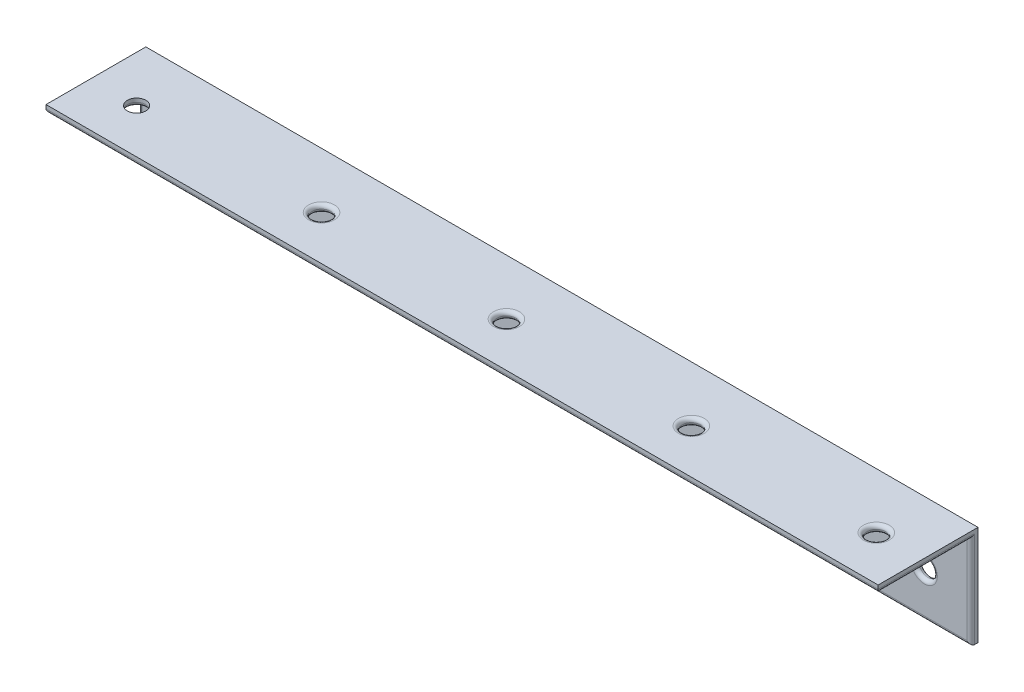
SolidWorks part; units mm, degrees
ref_plane "前视基准面" through (0, 0, 0) normal (0, 0, 1) x (1, 0, 0)
ref_plane "上视基准面" through (0, 0, 0) normal (0, 1, 0) x (1, 0, 0)
ref_plane "右视基准面" through (0, 0, 0) normal (1, 0, 0) x (0, 0, -1)
sketch "草图1" plane through (0, 0, 0) normal (0, 0, 1) x (1, 0, 0)
  line L1 (-112.5, 13.5) -> (112.5, 13.5)
  line L2 (-112.5, 13.5) -> (-112.5, -13.5)
  line L3 (-112.5, -13.5) -> (112.5, -13.5)
  line L4 (112.5, 13.5) -> (112.5, -13.5)
  line L5 (0, -13.5) -> (0, 13.5) construction
  line L6 (-112.5, 0) -> (112.5, 0) construction
  circle A0 centre (-100, -1.5) radius 2.5
  circle A4 centre (-50, -1.5) radius 2.5
  circle A5 centre (0, -1.5) radius 2.5
  circle A6 centre (50, -1.5) radius 2.5
  circle A7 centre (100, -1.5) radius 2.5
  point P0 (0, 0)
  dimension "D3" = 5
  dimension "D1" = 27
  dimension "D2" = 225
  dimension "D4" = 12.5
  dimension "D5" = 12
  dimension "D6" = 5
extrude "凸台-拉伸1" add sketch "草图1" along normal mid plane 2
sketch "草图2" plane through (0, 0, 1) normal (0, 0, 1) x (1, 0, 0)
  line L0 (112.5, -13.5) -> (112.5, 13.5) construction
  line L1 (-112.5, 13.5) -> (112.5, 13.5)
  line L2 (-112.5, 13.5) -> (-112.5, 11.5)
  line L3 (-112.5, 11.5) -> (112.5, 11.5)
  line L4 (112.5, 13.5) -> (112.5, 11.5)
  dimension "D1" = 2
extrude "凸台-拉伸2" add sketch "草图2" along normal blind 25
sketch "草图3" plane through (0, 11.5, 0) normal (0, -1, 0) x (1, 0, 0)
  line L0 (-112.5, 26) -> (112.5, 26) construction
  line L1 (-112.5, 26) -> (-112.5, 1) construction
  circle A0 centre (-100, 14) radius 2.5
  circle A1 centre (-50, 14) radius 2.5
  circle A2 centre (0, 14) radius 2.5
  circle A3 centre (50, 14) radius 2.5
  circle A4 centre (100, 14) radius 2.5
  dimension "D1" = 5
  dimension "D2" = 12
  dimension "D3" = 12.5
  dimension "D4" = 5
extrude "切除-拉伸1" cut sketch "草图3" against normal through all
fillet "圆角1" radius 1 24 edges at (-47.5, -1.5, 1) (100, 11.5, 11.5) (100, 13.5, 11.5) (102.5, -1.5, -1) (102.5, -1.5, 1) (50, 11.5, 11.5) (50, 13.5, 11.5) (2.5, -1.5, -1) (2.5, -1.5, 1) (0, 11.5, 11.5) (0, 13.5, 11.5) (-50, 11.5, 11.5) (-50, 13.5, 11.5) (-112.5, -1, 1) (-112.5, 11.5, 13.5) (0, -13.5, 1) (112.5, -1, 1) (112.5, 11.5, 13.5) (0, 11.5, 26) (52.5, -1.5, -1) (52.5, -1.5, 1) (-100, 11.5, 11.5) (-97.5, -1.5, -1) (-97.5, -1.5, 1)
